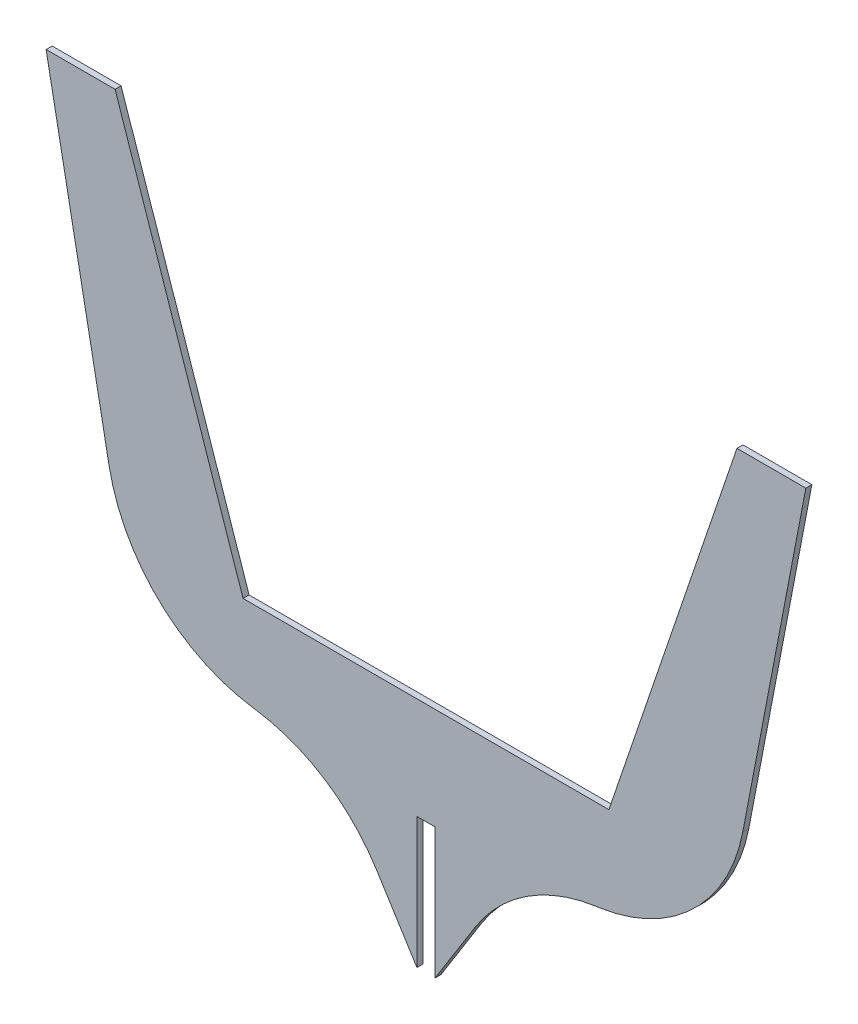
SolidWorks part; units mm, degrees
ref_plane "Plan de face" through (0, 0, 0) normal (0, 0, 1) x (1, 0, 0)
ref_plane "Plan de dessus" through (0, 0, 0) normal (0, 1, 0) x (1, 0, 0)
ref_plane "Plan de droite" through (0, 0, 0) normal (1, 0, 0) x (0, 0, -1)
sketch "Esquisse1" plane through (0, 0, 0) normal (0, 1, 0) x (1, 0, 0)
  point P0 (0, 27.1237)
sketch "Esquisse3" plane through (0, 0, 0) normal (0, 0, 1) x (1, 0, 0)
  line L49 (-89.6128, 1.004) -> (11.1623, -13.9262)
  line L50 (11.1623, -13.9262) -> (51.8853, -78.9262)
  line L51 (51.8853, -78.9262) -> (51.8853, -13.9262)
  line L52 (60.8853, -13.9262) -> (51.8853, -13.9262)
  line L54 (56.3853, -13.9262) -> (56.3853, 36.6646) construction
  line L55 (60.8853, -78.9262) -> (60.8853, -13.9262)
  line L56 (202.3834, 1.004) -> (101.6083, -13.9262)
  line L57 (245.0528, 223.8738) -> (202.3834, 1.004)
  line L61 (210.8251, 223.8738) -> (147.2298, 36.6646)
  line L63 (101.6083, -13.9262) -> (60.8853, -78.9262)
  line L65 (147.2298, 36.6646) -> (-34.4592, 36.6646)
  line L66 (210.8251, 223.8738) -> (245.0528, 223.8738)
  line L67 (-98.0545, 223.8738) -> (-132.2823, 223.8738)
  line L68 (-98.0545, 223.8738) -> (-34.4592, 36.6646)
  line L69 (-132.2823, 223.8738) -> (-89.6128, 1.004)
  point P2 (173.2999, -9.9307)
  point P3 (186.611, -11.6977)
  point P6 (207.9902, 98.1462)
  point P17 (123.5529, 59.4726)
  point P18 (184.1896, 284.6519)
  point P19 (200.3783, 285.7579)
  point P22 (125.9231, 58.6321)
  point P23 (215.5733, 76.095)
  point P24 (210.8251, 286.0738)
  point P25 (156.3759, 43.3473)
  point P26 (144.3613, -33.2148)
  point P27 (-8.939, -24.0535)
  point P28 (215.2093, 37.0224)
  point P29 (101.6083, -13.9262)
  point P30 (202.3834, 30.304)
  point P31 (147.2298, 36.6646)
  dimension "D2" = 237.8
  dimension "D6" = 9
  dimension "D11" = 65
extrude "Boss.-Extru.3" add sketch "Esquisse3" along normal blind 3
fillet "Congé2" radius 85 4 edges at (11.1623, -13.9262, 1.5) (-89.6128, 1.004, 1.5) (202.3834, 1.004, 1.5) (101.6083, -13.9262, 1.5)
